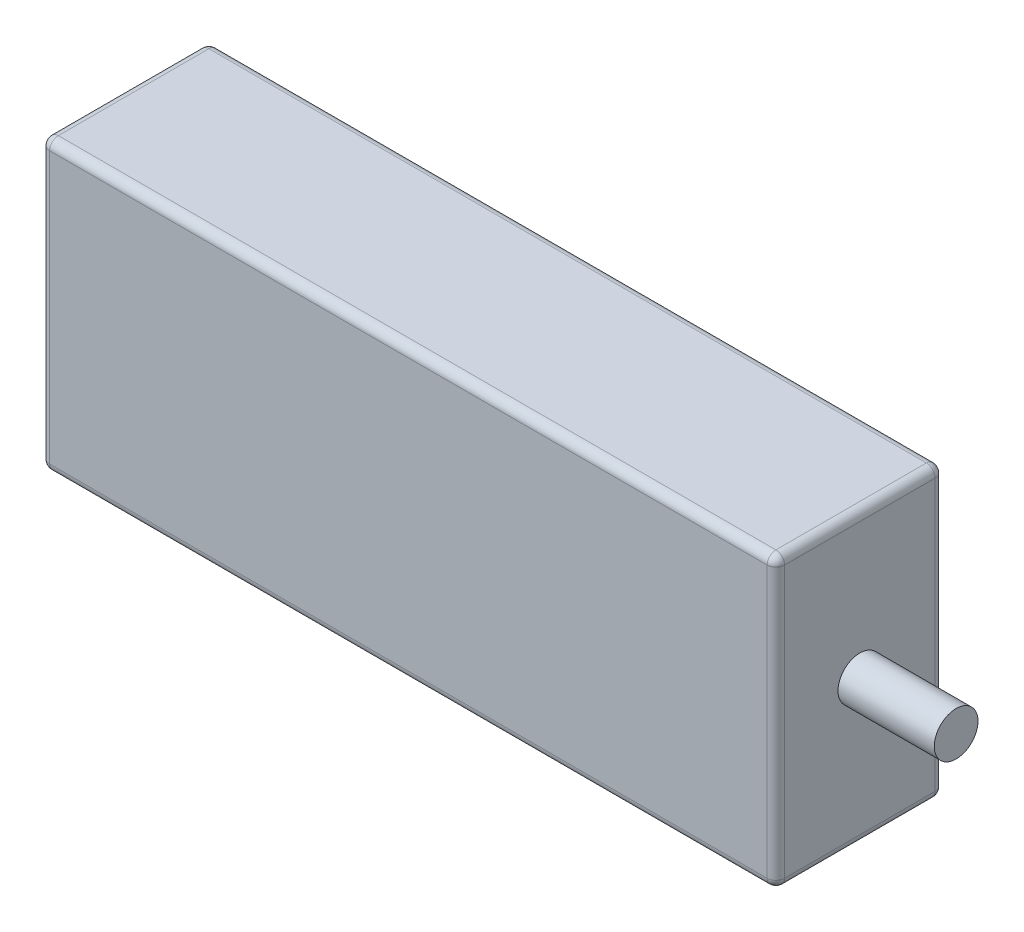
SolidWorks part; units mm, degrees
ref_plane "Plan de face" through (0, 0, 0) normal (0, 0, 1) x (1, 0, 0)
ref_plane "Plan de dessus" through (0, 0, 0) normal (0, 1, 0) x (1, 0, 0)
ref_plane "Plan de droite" through (0, 0, 0) normal (1, 0, 0) x (0, 0, -1)
sketch "Esquisse1" plane through (0, 0, 0) normal (0, 0, 1) x (1, 0, 0)
  line L1 (0, 0) -> (168, 0)
  line L2 (0, 0) -> (0, 66)
  line L3 (0, 66) -> (168, 66)
  line L4 (168, 0) -> (168, 66)
  dimension "D1" = 168
  dimension "D2" = 66
extrude "Boss.-Extru.1" add sketch "Esquisse1" along normal blind 38.4
fillet "Congé1" radius 2 12 edges at (0, 0, 19.2) (84, 0, 0) (0, 33, 0) (168, 0, 19.2) (168, 33, 0) (168, 66, 19.2) (0, 66, 19.2) (84, 66, 0) (84, 66, 38.4) (168, 33, 38.4) (84, 0, 38.4) (0, 33, 38.4)
sketch "Esquisse2" plane through (168, 0, 0) normal (1, 0, 0) x (0, 0, -1)
  line L0 (-19.2, 64) -> (-19.2, 2) construction
  line L1 (-2, 64) -> (-36.4, 64) construction
  line L2 (-36.4, 2) -> (-2, 2) construction
  circle A0 centre (-19.2, 33) radius 5
  point P8 (-19.2, 33)
  dimension "D1" = 10
extrude "Boss.-Extru.2" add sketch "Esquisse2" along normal blind 22
